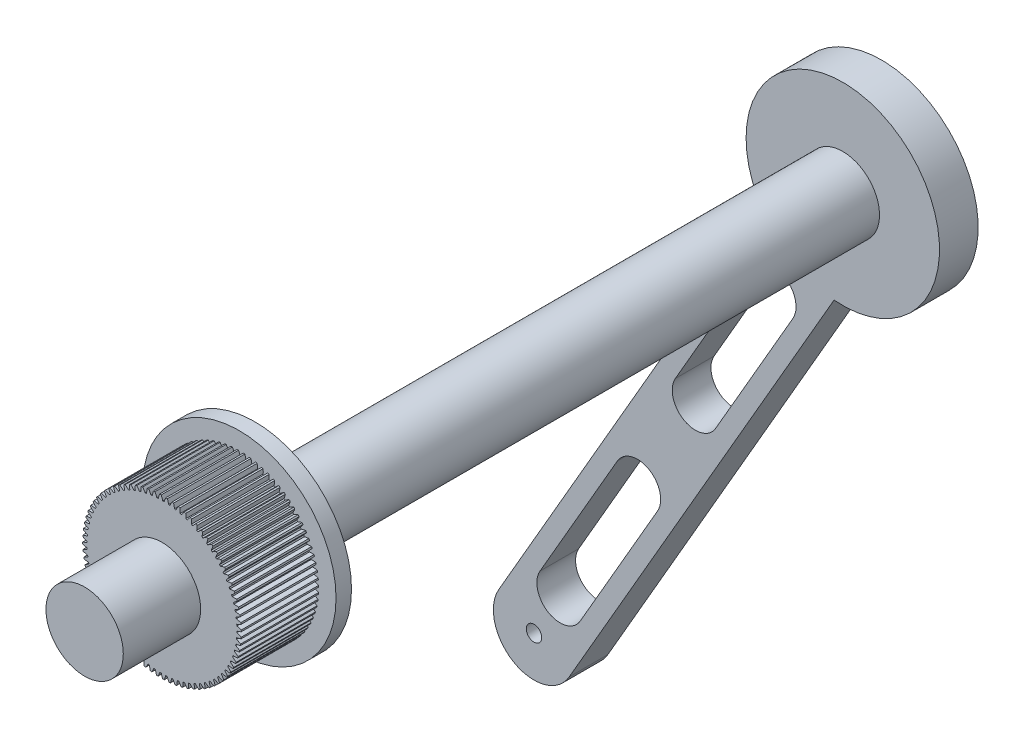
SolidWorks part; units mm, degrees
ref_plane "前视基准面" through (0, 0, 0) normal (0, 0, 1) x (1, 0, 0)
ref_plane "上视基准面" through (0, 0, 0) normal (0, 1, 0) x (1, 0, 0)
ref_plane "右视基准面" through (0, 0, 0) normal (1, 0, 0) x (0, 0, -1)
other "Configuration Table"
sketch "草图1" plane through (0, 0, 0) normal (0, 0, 1) x (1, 0, 0)
  circle A0 centre (0, 0) radius 125
  dimension "D1" = 250
extrude "凸台-拉伸1" add sketch "草图1" along normal blind 20 contours A0
sketch "草图2" plane through (0, 0, 20) normal (0, 0, 1) x (1, 0, 0)
  line L0 (0, 0) -> (0, -139.0454) construction
  line L1 (0, 0) -> (50.2474, -138.0537) construction
  line L2 (0, 0) -> (2.7702, -141.0661) construction
  line L3 (0, -100) -> (32.1394, -88.3022) construction
  arc A0 (-0.9721, -96.8701) -> (4.7744, -96.7573) centre (0, 0) ccw
  arc A1 (1.0211, -102.4949) -> (3.0036, -102.456) centre (0, 0) ccw
  circle A2 centre (0, 0) radius 100 construction
  arc A3 (-0.9721, -96.8701) -> (1.0211, -102.4949) centre (32.1394, -88.3022) ccw
  arc A4 (4.7744, -96.7573) -> (3.0036, -102.456) centre (-28.6479, -89.4959) cw
  dimension "D1" = 193.75
  dimension "D2" = 205
  dimension "D3" = 200
  dimension "D4" = 20
  dimension "D5" = 1.125
extrude "凸台-拉伸2" add sketch "草图2" along normal blind 100
pattern_circular "阵列(圆周)1" count 80 over 360 about axis through (0, 0, 20) along (0, 0, 1) of "凸台-拉伸2"
sketch "草图3" plane through (0, 0, 20) normal (0, 0, 1) x (1, 0, 0)
  circle A0 centre (0, 0) radius 96.875
extrude "凸台-拉伸3" add sketch "草图3" along normal blind 100
sketch "草图4" plane through (0, 0, 120) normal (0, 0, 1) x (1, 0, 0)
  circle A0 centre (0, 0) radius 50
  dimension "D1" = 100
extrude "凸台-拉伸4" add sketch "草图4" along normal blind 100
sketch "草图5" plane through (0, 0, 0) normal (0, 0, -1) x (-1, 0, 0)
  circle A0 centre (0, 0) radius 47.5
  dimension "D1" = 95
extrude "凸台-拉伸5" add sketch "草图5" along normal blind 760
sketch "草图6" plane through (0, 0, -760) normal (0, 0, -1) x (-1, 0, 0)
  line L0 (0, 0) -> (86.3616, -149.5826) construction
  line L1 (0, 0) -> (0, -125) construction
  line L2 (11.2539, -124.4924) -> (353.6714, -717.5768)
  line L5 (102.1866, -71.9924) -> (444.6041, -665.0768)
  arc A1 (0, -125) -> (102.1866, -71.9924) centre (0, 0) cw
  arc A2 (353.6714, -717.5768) -> (444.6041, -665.0768) centre (399.1377, -691.3268) ccw
  circle A3 centre (0, 0) radius 125 construction
  arc A4 (0, -125) -> (11.2539, -124.4924) centre (0, 0) ccw
  dimension "D1" = 30
  dimension "D2" = 105
  dimension "D3" = 800
extrude "凸台-拉伸6" add sketch "草图6" along normal blind 50
sketch "草图7" plane through (0, 0, -810) normal (0, 0, -1) x (-1, 0, 0)
  line L0 (0, 0) -> (455.2304, -788.4822) construction
  line L2 (190.429, -329.8327) -> (90.429, -156.6276) construction
  line L3 (164.4482, -344.8327) -> (64.4482, -171.6276)
  line L4 (216.4098, -314.8327) -> (116.4098, -141.6276)
  line L5 (265.429, -459.7365) -> (365.429, -632.9416) construction
  line L6 (291.4098, -444.7365) -> (391.4098, -617.9416)
  line L7 (239.4482, -474.7365) -> (339.4482, -647.9416)
  line L8 (182.4627, -421.0346) -> (273.3953, -368.5346) construction
  line L10 (11.2539, -124.4924) -> (353.6714, -717.5768) construction
  line L11 (444.6041, -665.0768) -> (102.1866, -71.9924) construction
  arc A0 (164.4482, -344.8327) -> (216.4098, -314.8327) centre (190.429, -329.8327) ccw
  arc A1 (116.4098, -141.6276) -> (64.4482, -171.6276) centre (90.429, -156.6276) ccw
  arc A2 (291.4098, -444.7365) -> (239.4482, -474.7365) centre (265.429, -459.7365) ccw
  arc A3 (339.4482, -647.9416) -> (391.4098, -617.9416) centre (365.429, -632.9416) ccw
  point P8 (140.429, -243.2302)
  point P13 (315.429, -546.3391)
  point P26 (164.8606, -681.6153)
  dimension "D1" = 75
  dimension "D2" = 200
  dimension "D3" = 200
  dimension "D4" = 60
  dimension "D5" = 60
extrude "切除-拉伸1" cut sketch "草图7" against normal through all
sketch "草图8" plane through (0, 0, -810) normal (0, 0, -1) x (-1, 0, 0)
  arc A0 (353.6714, -717.5768) -> (444.6041, -665.0768) centre (399.1377, -691.3268) ccw construction
  arc A1 (353.6714, -717.5768) -> (444.6041, -665.0768) centre (399.1377, -691.3268) ccw construction
  circle A2 centre (399.1377, -691.3268) radius 10
  dimension "D1" = 20
extrude "切除-拉伸2" cut sketch "草图8" against normal through all
